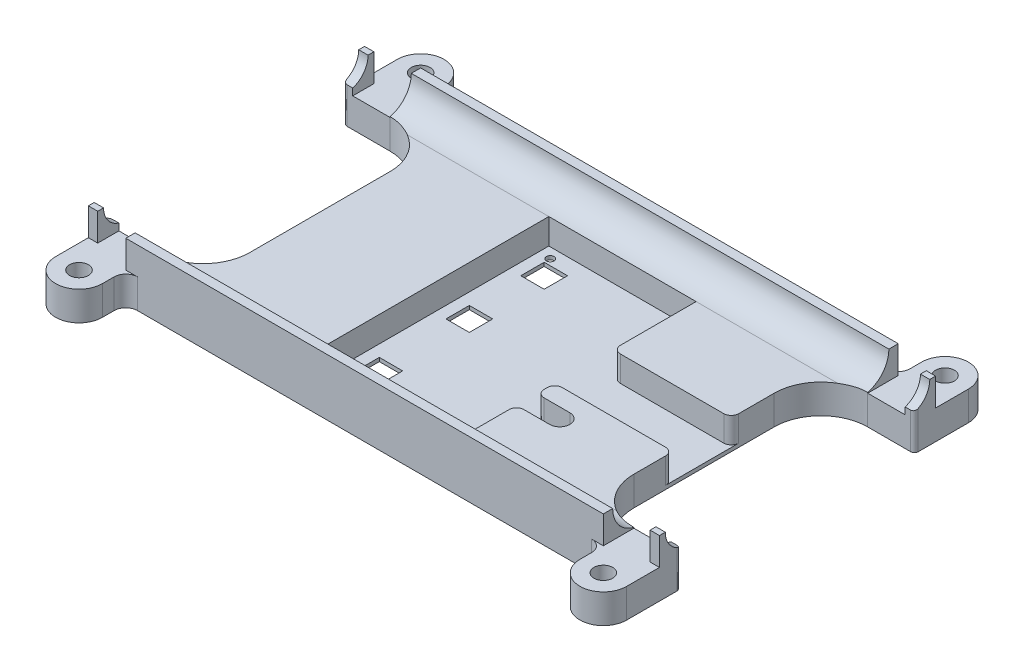
SolidWorks part; units mm, degrees
note: '?' marks a value the reader was unsure of.
material "Nylon 101"
ref_plane "Front Plane" through (0, 0, 0) normal (0, 0, 1) x (1, 0, 0)
ref_plane "Top Plane" through (0, 0, 0) normal (0, 1, 0) x (1, 0, 0)
ref_plane "Right Plane" through (0, 0, 0) normal (1, 0, 0) x (0, 0, -1)
ref_axis "X AXIS" through (-88.99, 0, 0) along (1, 0, 0)?
ref_axis "Y AXIS" through (0, -55, 0) along (0, 1, 0)?
ref_axis "Z AXIS" through (0, 0, 55) along (0, 0, -1)?
other "Freeze***"
sketch "Sketch1" plane through (0, 0, 0) normal (0, 1, 0) x (1, 0, 0)
  line L0 (77.54, -40.04) -> (77.54, 40.04)
  line L1 (-75, -37.5) -> (75, -37.5) construction
  line L2 (-75, -37.5) -> (-75, 37.5) construction
  line L3 (-75, 37.5) -> (75, 37.5) construction
  line L4 (75, -37.5) -> (75, 37.5) construction
  line L5 (0, 37.5) -> (0, -37.5) construction
  line L6 (-75, 0) -> (75, 0) construction
  line L7 (-64.84, 40.04) -> (64.84, 40.04)
  line L8 (-77.54, -40.04) -> (-77.54, 40.04)
  line L9 (-64.84, -40.04) -> (64.84, -40.04)
  line L10 (-77.54, 40.04) -> (-77.54, 46.39)
  line L11 (-64.84, 46.39) -> (-64.84, 40.04)
  line L12 (64.84, 46.39) -> (64.84, 40.04)
  line L13 (-77.54, 40.04) -> (77.54, 40.04) construction
  line L14 (77.54, 40.04) -> (77.54, 46.39)
  line L15 (77.54, -40.04) -> (77.54, -46.39)
  line L16 (64.84, -46.39) -> (64.84, -40.04)
  line L17 (-64.84, -46.39) -> (-64.84, -40.04)
  line L18 (-77.54, -40.04) -> (-77.54, -46.39)
  line L19 (-77.54, -40.04) -> (77.54, -40.04) construction
  arc A0 (-64.84, 46.39) -> (-77.54, 46.39) centre (-71.19, 46.39) ccw
  arc A1 (64.84, 46.39) -> (77.54, 46.39) centre (71.19, 46.39) cw
  arc A2 (64.84, -46.39) -> (77.54, -46.39) centre (71.19, -46.39) ccw
  arc A3 (-64.84, -46.39) -> (-77.54, -46.39) centre (-71.19, -46.39) cw
  point P0 (0, 0)
  dimension "D4" = 12.7
  dimension "D1" = 150
  dimension "D2" = 75
  dimension "D3" = 2.54
extrude "Boss-Extrude1" add sketch "Sketch1" along normal blind 7.9375
hole_wizard "#10 Clearance Hole1" positions "Sketch6" profile "Sketch7" hole size "#10" standard "ANSI Inch" end condition through all
sketch "Sketch6" plane through (0, 7.9375, 0) normal (0, 1, 0) x (1, 0, 0)
  point P0 (-71.19, 46.39)
  point P3 (71.19, 46.39)
  point P6 (71.19, -46.39)
  point P9 (-71.19, -46.39)
sketch "Sketch7" plane through (-71.19, 7.9375, -46.39) normal (1, 0, 0) x (0, 0, 1)
  line L0 (0, 0) -> (0, 7.9375)
  line L1 (0, 7.9375) -> (2.5527, 7.9375)
  line L2 (2.5527, 7.9375) -> (2.5527, 0)
  line L5 (2.5527, 0) -> (0, 0)
  line L11 (0, -6.35) -> (0, 107.95) construction
  dimension "Thru Hole Dia." = 5.1054
  dimension "Thru Hole Depth" = 7.9375
sketch "Sketch8" plane through (0, 7.9375, 0) normal (0, 1, 0) x (1, 0, 0)
  line L0 (-77.54, 46.39) -> (-77.54, -46.39) construction
  line L1 (-77.54, 37.5) -> (-75, 37.5)
  line L2 (-77.54, 37.5) -> (-77.54, 35.9125)
  line L3 (-77.54, 35.9125) -> (-75, 35.9125)
  line L4 (-75, 37.5) -> (-75, 35.9125)
  line L5 (64.84, 40.04) -> (-64.84, 40.04) construction
  line L6 (0, 0) -> (0, 40.04) construction
  line L7 (75, 37.5) -> (75, 35.9125)
  line L8 (77.54, 35.9125) -> (75, 35.9125)
  line L9 (77.54, 37.5) -> (77.54, 35.9125)
  line L10 (77.54, 37.5) -> (75, 37.5)
  line L11 (0, 0) -> (-77.54, 0) construction
  line L12 (77.54, -37.5) -> (75, -37.5)
  line L13 (77.54, -37.5) -> (77.54, -35.9125)
  line L14 (77.54, -35.9125) -> (75, -35.9125)
  line L15 (75, -37.5) -> (75, -35.9125)
  line L16 (-75, -37.5) -> (-75, -35.9125)
  line L17 (-77.54, -35.9125) -> (-75, -35.9125)
  line L18 (-77.54, -37.5) -> (-77.54, -35.9125)
  line L19 (-77.54, -37.5) -> (-75, -37.5)
  line L29 (64.84, 46.39) -> (64.84, 40.04) construction
  line L30 (-64.84, 40.04) -> (64.84, 40.04)
  line L31 (-64.84, 40.04) -> (-64.84, 37.5)
  line L32 (-64.84, 37.5) -> (64.84, 37.5)
  line L33 (64.84, 40.04) -> (64.84, 37.5)
  line L34 (-64.84, -40.04) -> (-64.84, -37.5)
  line L35 (-64.84, -40.04) -> (64.84, -40.04)
  line L36 (64.84, -40.04) -> (64.84, -37.5)
  line L37 (-64.84, -37.5) -> (64.84, -37.5)
  dimension "D1" = 2.54
  dimension "D2" = 1.5875
  dimension "D3" = 2.54
extrude "Boss-Extrude2" add sketch "Sketch8" along normal blind 7.5
sketch "Sketch10" plane through (0, 7.9375, 0) normal (0, 1, 0) x (1, 0, 0)
  line L0 (0, 0) -> (0, 40.04) construction
  line L1 (-77.54, 35.9125) -> (-75, 35.9125)
  line L2 (-77.54, 35.9125) -> (-77.54, -35.9125)
  line L3 (-77.54, -35.9125) -> (-75, -35.9125)
  line L4 (-75, 35.9125) -> (-75, -35.9125)
  line L5 (64.84, 40.04) -> (-64.84, 40.04) construction
  line L6 (77.54, 35.9125) -> (75, 35.9125)
  line L7 (77.54, 35.9125) -> (77.54, -35.9125)
  line L8 (77.54, -35.9125) -> (75, -35.9125)
  line L9 (75, 35.9125) -> (75, -35.9125)
extrude "Boss-Extrude3" add sketch "Sketch10" along normal blind 1.5875
fillet "Fillet3" radius 3.175 4 edges at (64.84, 3.9688, -40.04) (-64.84, 3.9688, -40.04) (64.84, 3.9688, 40.04) (-64.84, 3.9688, 40.04)
fillet "Fillet4" radius 5.9125 4 edges at (76.27, 9.525, 35.9125) (76.27, 9.525, -35.9125) (-76.27, 9.525, 35.9125) (-76.27, 9.525, -35.9125)
fillet "Fillet5" radius 7.5 2 edges at (0, 7.9375, 37.5) (0, 7.9375, -37.5)
sketch "Sketch11" plane through (0, 0, 0) normal (0, -1, 0) x (1, 0, 0)
  line L0 (-77.54, -46.39) -> (-77.54, 46.39) construction
  line L1 (-77.54, 31.75) -> (-52.14, 31.75)
  line L2 (-77.54, 31.75) -> (-77.54, -31.75)
  line L3 (-77.54, -31.75) -> (-52.14, -31.75)
  line L4 (-52.14, 31.75) -> (-52.14, -31.75)
  line L5 (0, 0) -> (0, 40.04) construction
  line L6 (-61.665, 40.04) -> (61.665, 40.04) construction
  line L7 (52.14, 31.75) -> (52.14, -31.75)
  line L8 (77.54, -31.75) -> (52.14, -31.75)
  line L9 (77.54, 31.75) -> (77.54, -31.75)
  line L10 (77.54, 31.75) -> (52.14, 31.75)
  point P6 (-52.14, 0)
  dimension "D1" = 63.5
  dimension "D2" = 25.4
extrude "Cut-Extrude1" cut sketch "Sketch11" against normal through all
fillet "Fillet6" radius 12.7 4 edges at (52.14, 4.0723, -31.75) (52.14, 4.0723, 31.75) (-52.14, 4.0723, -31.75) (-52.14, 4.0723, 31.75)
sketch "Sketch12" plane through (0, 7.9375, 0) normal (0, 1, 0) x (1, 0, 0)
  line L1 (-20, -30) -> (20, -30)
  line L2 (-20, -30) -> (-20, 30)
  line L3 (-20, 30) -> (20, 30)
  line L4 (20, -30) -> (20, 30)
  line L5 (0, 30) -> (0, -30) construction
  line L6 (-20, 0) -> (20, 0) construction
  point P0 (0, 0)
  dimension "D1" = 60
  dimension "D2" = 40
extrude "Cut-Extrude2" cut sketch "Sketch12" against normal offset from surface (6.9375 mm away) 1 up to face at (-71.19, 0, -43.8373)
sketch "Sketch13" plane through (0, 7.9375, 0) normal (0, 1, 0) x (1, 0, 0)
  line L0 (20, -30) -> (20, 30) construction
  line L1 (20, 7.4) -> (77.54, 7.4)
  line L2 (20, 7.4) -> (20, -8.4)
  line L3 (20, -8.4) -> (77.54, -8.4)
  line L4 (77.54, 7.4) -> (77.54, -8.4)
  line L5 (-20, -30) -> (20, -30) construction
  line L6 (-20, 30) -> (20, 30) construction
  line L7 (77.54, 37.5) -> (77.54, 46.39) construction
  point P10 (0, 0)
  point P11 (0, 0)
  point P13 (0, 0)
  point P15 (0, 0)
  dimension "D1" = 21.6
  dimension "D2" = 22.6
extrude "Cut-Extrude3" cut sketch "Sketch13" against normal up to surface (6.9375 mm away) up to face at (0, 1, 0)
sketch "Sketch14" plane through (0, 7.9375, 0) normal (0, 1, 0) x (1, 0, 0)
  line L0 (29, -16.03) -> (20, -16.03) construction
  line L1 (29, -18.78) -> (20, -18.78)
  line L2 (29, -13.28) -> (20, -13.28)
  line L3 (20, 30) -> (20, 7.4) construction
  line L5 (-20, -30) -> (20, -30) construction
  arc A0 (29, -18.78) -> (29, -13.28) centre (29, -16.03) ccw
  arc A1 (20, -13.28) -> (20, -18.78) centre (20, -16.03) ccw
  point P2 (24.5, -16.03)
  point P7 (0, 0)
  dimension "D1" = 5.5
  dimension "D2" = 9
  dimension "D3" = 13.97
extrude "Cut-Extrude4" cut sketch "Sketch14" against normal through all
sketch "Sketch15" plane through (0, 1, 0) normal (0, 1, 0) x (1, 0, 0)
  line L0 (-16.825, -1.115) -> (-10.475, -1.115)
  line L1 (-20, 30) -> (-20, -30) construction
  line L2 (-16.825, 19.205) -> (-10.475, 19.205)
  line L3 (-16.825, 19.205) -> (-16.825, 25.555)
  line L4 (-16.825, 25.555) -> (-10.475, 25.555)
  line L5 (-10.475, 19.205) -> (-10.475, 25.555)
  line L6 (-13.65, 25.555) -> (-13.65, 19.205) construction
  line L7 (-16.825, 22.38) -> (-10.475, 22.38) construction
  line L8 (-20, 30) -> (20, 30) construction
  line L9 (-16.825, -1.115) -> (-16.825, 5.235)
  line L10 (-16.825, 5.235) -> (-10.475, 5.235)
  line L11 (-10.475, -1.115) -> (-10.475, 5.235)
  line L12 (-13.65, 5.235) -> (-13.65, -1.115) construction
  line L13 (-16.825, 2.06) -> (-10.475, 2.06) construction
  line L14 (20, -30) -> (-20, -30) construction
  line L15 (-16.825, -19.205) -> (-10.475, -19.205)
  line L16 (-16.825, -19.205) -> (-16.825, -25.555)
  line L17 (-16.825, -25.555) -> (-10.475, -25.555)
  line L18 (-10.475, -19.205) -> (-10.475, -25.555)
  line L19 (-13.65, -25.555) -> (-13.65, -19.205) construction
  line L20 (-16.825, -22.38) -> (-10.475, -22.38) construction
  point P0 (-13.65, 22.38)
  point P8 (-13.65, 2.06)
  point P17 (-11.4743, -14.3952)
  point P18 (0, 0)
  point P19 (-13.65, -22.38)
  dimension "D2" = 6.35
  dimension "D1" = 6.35
  dimension "D3" = 7.62
  dimension "D4" = 20.32
  dimension "D5" = 7.62
extrude "Cut-Extrude5" cut sketch "Sketch15" against normal through all
fillet "Fillet7" radius 2.032 6 edges at (20, 4.4688, 18.78) (20, 4.4688, 13.28) (20, 4.4688, -7.4) (20, 4.4688, 8.4) (52.14, 4.4688, -7.4) (52.14, 4.4688, 8.4)
hole_wizard "#45 (0.082) Diameter Hole1" positions "Sketch16" profile "Sketch17" hole size "#45" standard "ANSI Inch" end condition through all
sketch "Sketch16" plane through (0, 1, 0) normal (0, 1, 0) x (1, 0, 0)
  line L1 (-16.825, 27.206) -> (16.825, 27.206)
  line L2 (-16.825, 27.206) -> (-16.825, -27.46)
  line L3 (-16.825, -27.46) -> (16.825, -27.46)
  line L4 (16.825, 27.206) -> (16.825, -27.46)
  line L5 (20, 30) -> (-20, 30) construction
  line L6 (-20, -30) -> (20, -30) construction
  line L7 (-20, 30) -> (-20, -30) construction
  line L8 (20, 30) -> (20, 9.432) construction
  point P0 (-16.825, 27.206)
  point P4 (16.825, -27.46)
  point P57 (-16.825, -27.46)
  point P58 (16.825, 27.206)
  dimension "D1" = 2.794
  dimension "D2" = 2.54
  dimension "D3" = 3.175
  dimension "D4" = 3.175
sketch "Sketch17" plane through (-16.825, 1, -27.206) normal (1, 0, 0) x (0, 0, 1)
  line L0 (0, 0) -> (0, 1)
  line L1 (0, 1) -> (1.0414, 1)
  line L2 (1.0414, 1) -> (1.0414, 0)
  line L5 (1.0414, 0) -> (0, 0)
  line L11 (0, -6.35) -> (0, 107.95) construction
  dimension "Thru Hole Dia." = 2.0828
  dimension "Thru Hole Depth" = 1
fillet "Fillet8" radius 1.016 4 edges at (-77.54, 4.895, -31.75) (-77.54, 4.895, 31.75) (77.54, 4.895, 31.75) (77.54, 4.895, -31.75)
